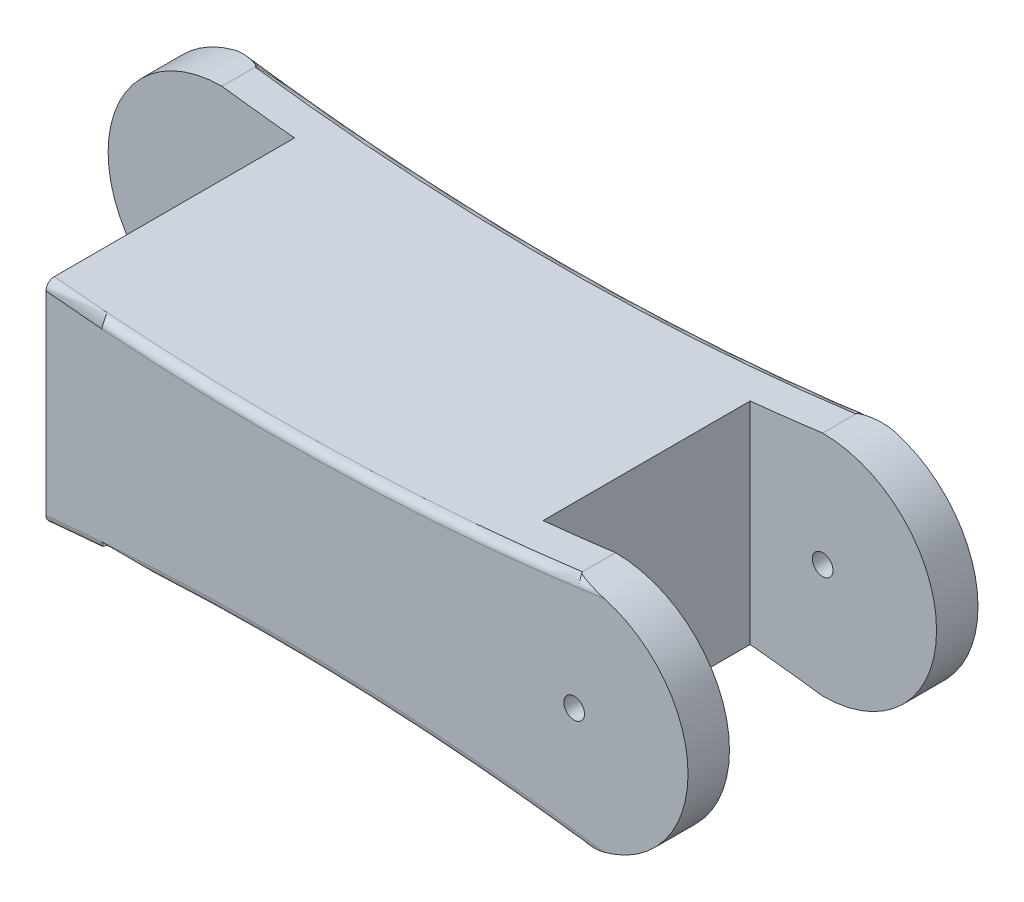
SolidWorks part; units mm, degrees
ref_plane "Front Plane" through (0, 0, 0) normal (0, 0, 1) x (1, 0, 0)
ref_plane "Top Plane" through (0, 0, 0) normal (0, 1, 0) x (1, 0, 0)
ref_plane "Right Plane" through (0, 0, 0) normal (1, 0, 0) x (0, 0, -1)
sketch "Sketch1" plane through (0, 0, 0) normal (0, 1, 0) x (1, 0, 0)
  line L1 (-100, -35) -> (100, -35)
  line L2 (-100, -35) -> (-100, 35)
  line L3 (-100, 35) -> (100, 35)
  line L4 (100, -35) -> (100, 35)
  line L5 (-100, -35) -> (100, 35) construction
  line L6 (-100, 35) -> (100, -35) construction
  point P0 (0, 0)
  dimension "D1" = 200
  dimension "D2" = 70
extrude "Boss-Extrude1" add sketch "Sketch1" along normal blind 55
sketch "Sketch3" plane through (0, 0, 0) normal (0, 0, 1) x (1, 0, 0)
  line L0 (-100, 0) -> (-100, 55)
  line L1 (100, 55) -> (55, 55)
  line L2 (-55, 55) -> (-100, 55)
  line L4 (-100, 0) -> (-55, 0)
  line L5 (0, 0) -> (0, 55) construction
  line L6 (-100, 55) -> (100, 55) construction
  line L8 (100, 55) -> (100, 0)
  line L10 (-55, 0) -> (-55, 55)
  line L11 (100, 55) -> (-100, 55) construction
  line L13 (55, 55) -> (55, 0)
  line L14 (-100, 0) -> (100, 0) construction
  line L15 (55, 0) -> (100, 0)
  dimension "D1" = 45
  dimension "D4" = 45
extrude "Cut-Extrude1" cut sketch "Sketch3" against normal mid plane 50
sketch "Sketch4" plane through (0, 0, 35) normal (0, 0, 1) x (1, 0, 0)
  line L0 (-100, 55) -> (-100, 0) construction
  line L1 (-100, 55) -> (100, 55) construction
  line L2 (0, 0) -> (0, 55) construction
  line L3 (-72.5, 27.5) -> (72.5, 27.5) construction
  line L4 (100, 55) -> (100, 0) construction
  line L5 (-100, 0) -> (100, 0) construction
  arc A0 (-72.5, 55) -> (-72.5, 0) centre (-72.5, 27.5) ccw
  arc A1 (72.5, 55) -> (72.5, 0) centre (72.5, 27.5) cw
  arc A2 (72.5, 55) -> (-72.5, 55) centre (0, 600.2007) cw
  arc A3 (72.5, 0) -> (-72.5, 0) centre (0, -545.2007) ccw
  dimension "D4" = 550
extrude "Cut-Extrude2" cut sketch "Sketch4" against normal through all both and the other way through all flip side to cut
fillet "Fillet2" radius 2 4 edges at (0, 50.2007, -35) (0, 4.7993, -35) (0, 50.2007, 35) (0, 4.7993, 35)
sketch "Sketch7" plane through (0, 0, 35) normal (0, 0, 1) x (1, 0, 0)
  line L0 (0, 0) -> (0, 71.1105) construction
  circle A1 centre (72.5, 27.5) radius 2.5
  point P0 (78.85, 21.15)
  point P10 (78.85, 21.15)
  dimension "D1" = 5
extrude "Cut-Extrude3" cut sketch "Sketch7" against normal through all both and the other way through all
sketch "Sketch8" plane through (0, 0, 25) normal (0, 0, -1) x (-1, 0, 0)
  line L0 (55, 2.0424) -> (55, 52.9576) construction
  line L1 (55, -17.2616) -> (122.6049, -17.2616)
  line L2 (55, -17.2616) -> (55, 109.2298)
  line L3 (55, 109.2298) -> (122.6049, 109.2298)
  line L4 (122.6049, -17.2616) -> (122.6049, 109.2298)
  dimension "D1" = 0
extrude "Cut-Extrude4" cut sketch "Sketch8" against normal blind 50
sketch "Sketch10" plane through (0, 0, -25) normal (0, 0, 1) x (1, 0, 0)
  line L0 (-55, 50.9475) -> (-55, 4.0525) construction
  circle A0 centre (-76.15, 27.5) radius 2.5
  arc A1 (-72.5, 55) -> (-72.5, 0) centre (-72.5, 27.5) ccw construction
  point P8 (-100, 27.5)
  dimension "D2" = 5
  dimension "D3" = 0
  dimension "D1" = 21.15
extrude "Cut-Extrude5" cut sketch "Sketch10" against normal blind 50
